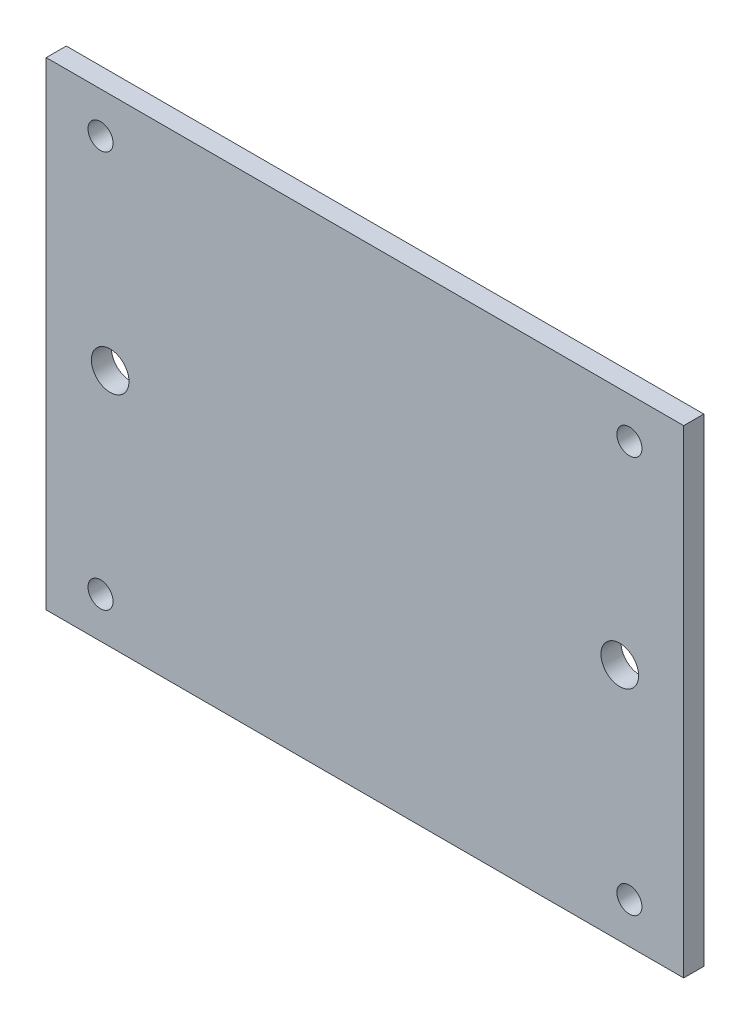
SolidWorks part; units mm, degrees
ref_plane "Front Plane" through (0, 0, 0) normal (0, 0, 1) x (1, 0, 0)
ref_plane "Top Plane" through (0, 0, 0) normal (0, 1, 0) x (1, 0, 0)
ref_plane "Right Plane" through (0, 0, 0) normal (1, 0, 0) x (0, 0, -1)
sketch "Sketch1" plane through (0, 0, 0) normal (0, 0, 1) x (1, 0, 0)
  line L0 (0, -40.427) -> (0, 40.427) construction
  line L1 (-25.42, -19.075) -> (25.42, -19.075)
  line L2 (-25.42, -19.075) -> (-25.42, 19.075)
  line L3 (-25.42, 19.075) -> (25.42, 19.075)
  line L4 (25.42, -19.075) -> (25.42, 19.075)
  line L5 (-25.42, -19.075) -> (25.42, 19.075) construction
  line L6 (-25.42, 19.075) -> (25.42, -19.075) construction
  line L7 (-52.9839, 0) -> (52.9839, 0) construction
  circle A2 centre (-21.0889, 15.825) radius 1
  circle A3 centre (21.0889, 15.825) radius 1
  circle A4 centre (21.0889, -15.825) radius 1
  circle A5 centre (-21.0889, -15.825) radius 1
  circle A6 centre (-20.32, 0) radius 1.5
  circle A7 centre (20.32, 0) radius 1.5
  point P0 (0, 0)
  point P9 (0, 0)
  point P14 (0, 0)
  dimension "D5" = 2
  dimension "D7" = 3
  dimension "D8" = 5.1
  dimension "D1" = 50.84
  dimension "D2" = 38.15
  dimension "D6" = 3.25
extrude "Boss-Extrude1" add sketch "Sketch1" along normal blind 1.6
